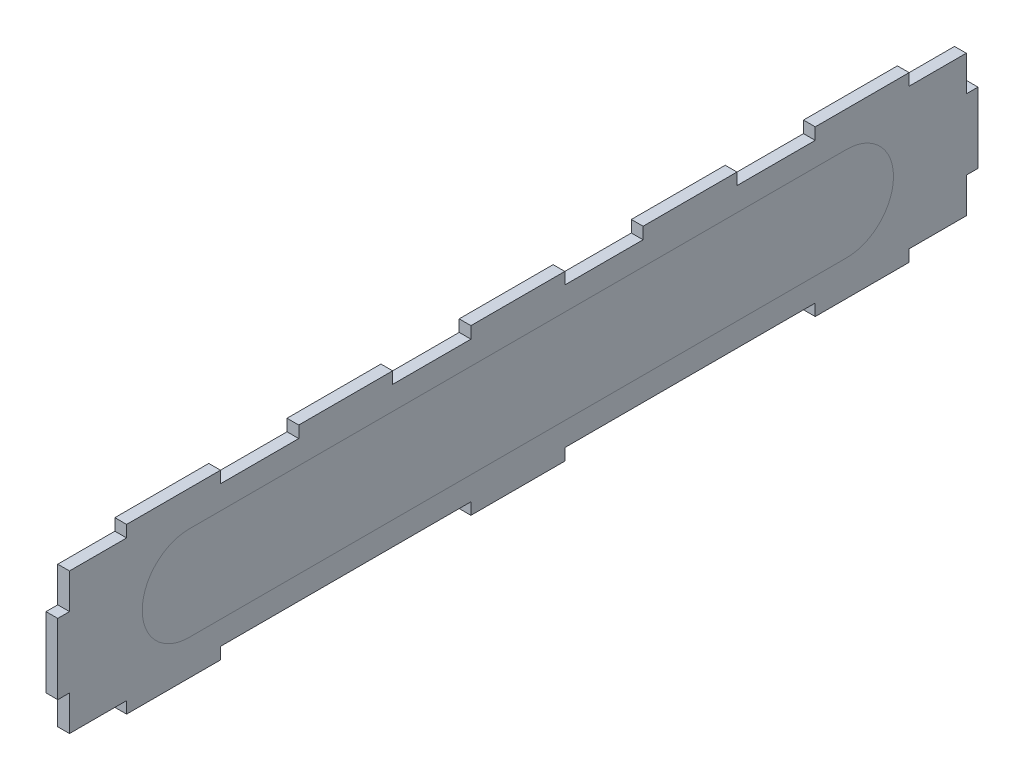
SolidWorks part; units mm, degrees
material "Maple"
ref_plane "Front Plane" through (0, 0, 0) normal (0, 0, 1) x (1, 0, 0)
ref_plane "Top Plane" through (0, 0, 0) normal (0, 1, 0) x (1, 0, 0)
ref_plane "Right Plane" through (0, 0, 0) normal (1, 0, 0) x (0, 0, -1)
sketch "Sketch1" plane through (0, 0, 0) normal (1, 0, 0) x (0, 0, -1)
  line L0 (-98, -17.5) -> (-98, 17.5) construction
  line L1 (-95.5, -15) -> (95.5, -15) construction
  line L2 (-95.5, -15) -> (-95.5, 15) construction
  line L3 (-95.5, 15) -> (95.5, 15) construction
  line L4 (95.5, -15) -> (95.5, 15) construction
  line L5 (-95.5, -15) -> (95.5, 15) construction
  line L6 (-95.5, 15) -> (95.5, -15) construction
  line L7 (-98, 17.5) -> (98, 17.5) construction
  line L8 (98, -17.5) -> (98, 17.5) construction
  line L9 (-98, -17.5) -> (98, -17.5) construction
  line L10 (-100, 22.5) -> (-100, -22.5) construction
  line L11 (0, -12.7783) -> (0, 11.2959) construction
  line L12 (100, 22.5) -> (100, -22.5) construction
  line L13 (10, -17.5) -> (-10, -17.5)
  line L14 (-10, -17.5) -> (-10, -15)
  line L15 (-10, -15) -> (-26.6667, -15)
  line L16 (-26.6667, -15) -> (-26.6667, -17.5) construction
  line L17 (-26.6667, -17.5) -> (-46.6667, -17.5) construction
  line L18 (-46.6667, -17.5) -> (-46.6667, -15) construction
  line L19 (-46.6667, -15) -> (-63.3333, -15)
  line L20 (-63.3333, -15) -> (-63.3333, -17.5)
  line L21 (-63.3333, -17.5) -> (-83.3333, -17.5)
  line L22 (-83.3333, -17.5) -> (-83.3333, -15)
  line L23 (-83.3333, -15) -> (-95.5, -15)
  line L24 (-95.5, -15) -> (-95.5, -7.5)
  line L25 (-95.5, -7.5) -> (-98, -7.5)
  line L26 (-98, -7.5) -> (-98, 7.5)
  line L27 (-19.2126, 0) -> (21.2755, 0) construction
  line L28 (-95.5, 7.5) -> (-98, 7.5)
  line L29 (-95.5, 15) -> (-95.5, 7.5)
  line L30 (-83.3333, 15) -> (-95.5, 15)
  line L31 (-83.3333, 17.5) -> (-83.3333, 15)
  line L32 (-63.3333, 17.5) -> (-83.3333, 17.5)
  line L33 (-63.3333, 15) -> (-63.3333, 17.5)
  line L34 (-46.6667, 15) -> (-63.3333, 15)
  line L35 (-46.6667, 17.5) -> (-46.6667, 15)
  line L36 (-26.6667, 17.5) -> (-46.6667, 17.5)
  line L37 (-26.6667, 15) -> (-26.6667, 17.5)
  line L38 (-10, 15) -> (-26.6667, 15)
  line L39 (-10, 17.5) -> (-10, 15)
  line L40 (10, 17.5) -> (-10, 17.5)
  line L41 (10, 17.5) -> (10, 15)
  line L42 (10, 15) -> (26.6667, 15)
  line L43 (26.6667, 15) -> (26.6667, 17.5)
  line L44 (26.6667, 17.5) -> (46.6667, 17.5)
  line L45 (46.6667, 17.5) -> (46.6667, 15)
  line L46 (46.6667, 15) -> (63.3333, 15)
  line L47 (63.3333, 15) -> (63.3333, 17.5)
  line L48 (63.3333, 17.5) -> (83.3333, 17.5)
  line L49 (83.3333, 17.5) -> (83.3333, 15)
  line L50 (83.3333, 15) -> (95.5, 15)
  line L51 (95.5, 15) -> (95.5, 7.5)
  line L52 (95.5, 7.5) -> (98, 7.5)
  line L53 (98, -7.5) -> (98, 7.5)
  line L54 (95.5, -7.5) -> (98, -7.5)
  line L55 (95.5, -15) -> (95.5, -7.5)
  line L56 (83.3333, -15) -> (95.5, -15)
  line L57 (83.3333, -17.5) -> (83.3333, -15)
  line L58 (63.3333, -17.5) -> (83.3333, -17.5)
  line L59 (63.3333, -15) -> (63.3333, -17.5)
  line L60 (46.6667, -15) -> (63.3333, -15)
  line L61 (46.6667, -17.5) -> (46.6667, -15) construction
  line L62 (26.6667, -17.5) -> (46.6667, -17.5) construction
  line L63 (26.6667, -15) -> (26.6667, -17.5) construction
  line L64 (10, -15) -> (26.6667, -15)
  line L65 (10, -17.5) -> (10, -15)
  line L66 (-83.3333, 15) -> (-100, 15)
  line L67 (-70, 0) -> (70, 0) construction
  line L68 (-70, 10) -> (70, 10)
  line L69 (-70, -10) -> (70, -10)
  line L70 (-46.6667, -15) -> (-26.6667, -15)
  line L71 (46.6667, -15) -> (26.6667, -15)
  arc A0 (-70, 10) -> (-70, -10) centre (-70, 0) ccw
  arc A1 (70, -10) -> (70, 10) centre (70, 0) ccw
  point P0 (0, 0)
  point P33 (-98, 0)
  point P46 (0, 17.5)
  point P69 (0, -17.5)
  point P72 (0, 0)
  dimension "D7" = 10
  dimension "D1" = 191
  dimension "D2" = 30
  dimension "D4" = 100
  dimension "D5" = 20
  dimension "D6" = 140
  dimension "D8" = 15
  dimension "D3" = 2.5
extrude "Boss-Extrude1" add sketch "Sketch1" along normal mid plane 2.5 contours L13 L65 L64 L63 L62 L61 L60 L59 L58 L57 L56 L55 L54 L53 L52 L51 L50 L49 L48 L47 L46 L45 L44 L43 L42 L41 L40 L39 L38 L37 L36 L35 L34 L33 L32 L31 L30 L29 L28 L26 L25 L24 L23 L22 L21 L20 L19 L18 L17 L16 L15 region at (0, -15.509, 0)
extrude "Boss-Extrude2" add sketch "Sketch1<6>" along normal mid plane 2.5 separate body contours L69 A1 L68 A0 region at (0, 0, 0)
sketch "Sketch1<6>" plane through (0, 0, 0) normal (1, 0, 0) x (0, 0, -1) same geometry as "Sketch1"
